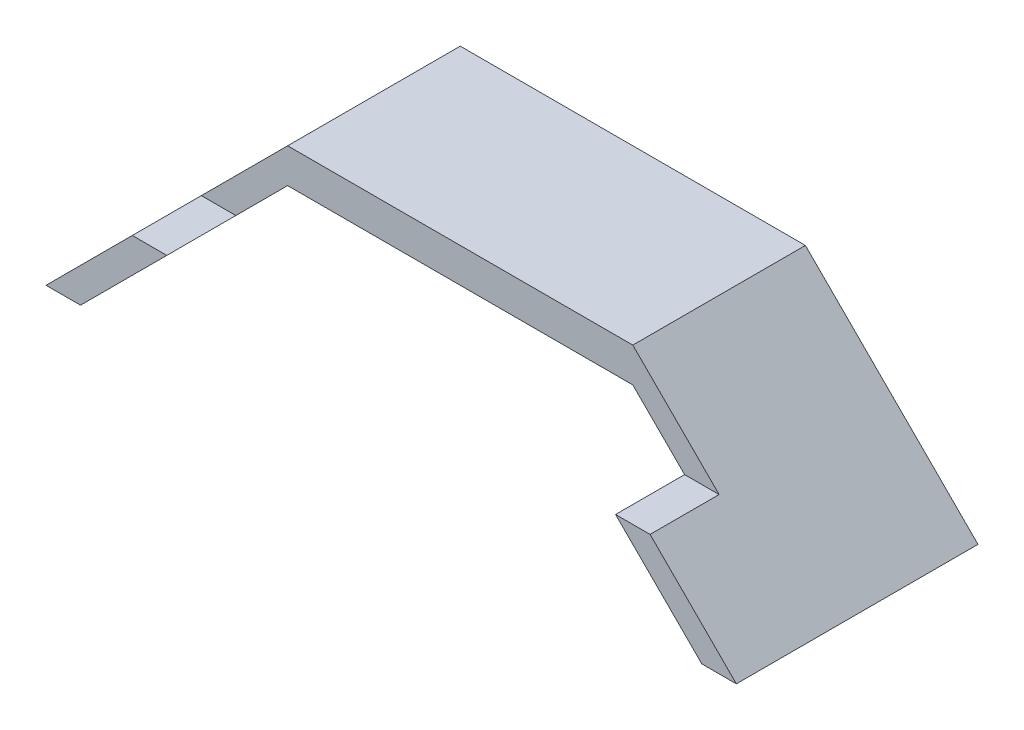
SolidWorks part; units mm, degrees
ref_plane "前视基准面" through (0, 0, 0) normal (0, 0, 1) x (1, 0, 0)
ref_plane "上视基准面" through (0, 0, 0) normal (0, 1, 0) x (1, 0, 0)
ref_plane "右视基准面" through (0, 0, 0) normal (1, 0, 0) x (0, 0, -1)
sketch "草图2" plane through (0, 0, 0) normal (0, 0, 1) x (1, 0, 0)
  line L0 (-150.8883, 26.3504) -> (-100.8883, 76.3504)
  line L1 (-100.8883, 76.3504) -> (-0.8883, 76.3504)
  line L3 (-150.8883, 26.3504) -> (-140.8883, 26.3504)
  line L5 (49.1117, 26.3504) -> (-0.8883, 76.3504)
  line L6 (-140.8883, 26.3504) -> (-100.8883, 66.3504)
  line L7 (-100.8883, 66.3504) -> (-0.8883, 66.3504)
  line L8 (-0.8883, 66.3504) -> (39.1117, 26.3504)
  line L9 (39.1117, 26.3504) -> (49.1117, 26.3504)
  dimension "D1" = 200
  dimension "D2" = 100
  dimension "D3" = 50
  dimension "D4" = 100
  dimension "D5" = 10
  dimension "D6" = 10
  dimension "D7" = 10
extrude "凸台-拉伸1" add sketch "草图2" along normal blind 70
sketch "草图3" plane through (0, 0, 70) normal (0, 0, 1) x (1, 0, 0)
  line L0 (49.1117, 26.3504) -> (-0.8883, 76.3504) construction
  line L1 (-100.8883, 76.3504) -> (-0.8883, 76.3504)
  line L3 (14.1117, 51.3504) -> (24.1117, 51.3504)
  line L5 (-100.8883, 76.3504) -> (-150.8883, 26.3504) construction
  line L6 (-125.8883, 51.3504) -> (-115.8883, 51.3504)
  line L10 (-125.8883, 51.3504) -> (-100.8883, 76.3504)
  line L11 (-100.8883, 66.3504) -> (-115.8883, 51.3504)
  line L12 (-140.8883, 26.3504) -> (-100.8883, 66.3504) construction
  line L13 (-100.8883, 66.3504) -> (-0.8883, 66.3504)
  line L14 (-0.8883, 66.3504) -> (14.1117, 51.3504)
  line L15 (-0.8883, 66.3504) -> (39.1117, 26.3504) construction
  line L16 (24.1117, 51.3504) -> (-0.8883, 76.3504)
  point P2 (0, 0)
extrude "切除-拉伸1" cut sketch "草图3" against normal blind 20
